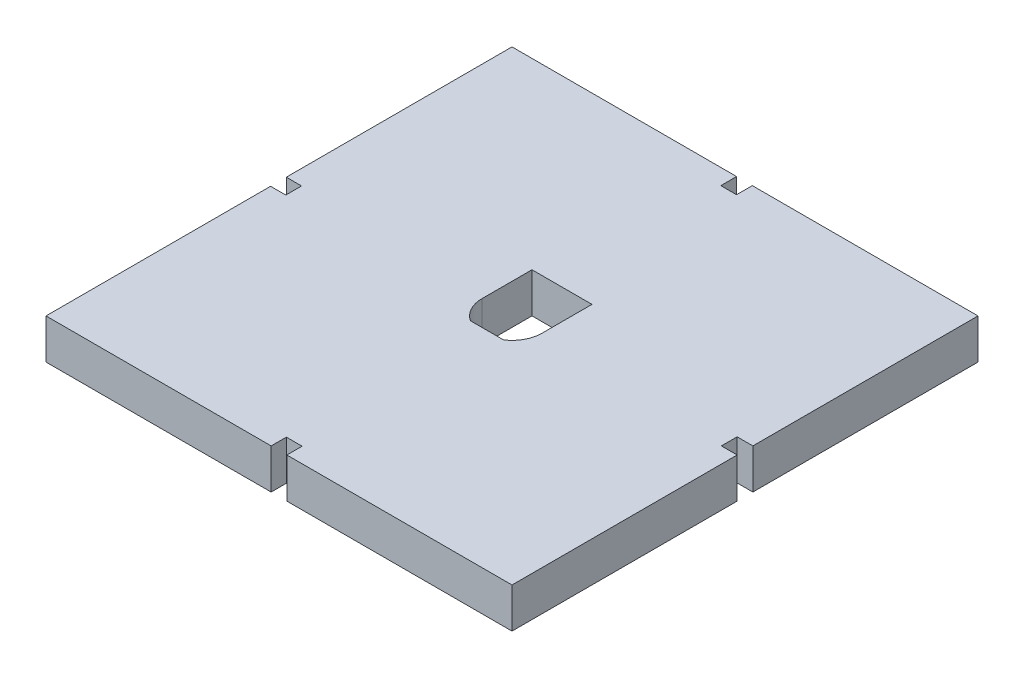
SolidWorks part; units mm, degrees
ref_plane "Front Plane" through (0, 0, 0) normal (0, 0, 1) x (1, 0, 0)
ref_plane "Top Plane" through (0, 0, 0) normal (0, 1, 0) x (1, 0, 0)
ref_plane "Right Plane" through (0, 0, 0) normal (1, 0, 0) x (0, 0, -1)
sketch "Sketch1" plane through (0, 0, 0) normal (0, 1, 0) x (1, 0, 0)
  line L1 (0, 0) -> (148, 0)
  line L2 (0, 0) -> (0, 148)
  line L3 (0, 148) -> (148, 148)
  line L4 (148, 0) -> (148, 148)
  dimension "D1" = 148
  dimension "D2" = 148
extrude "Boss-Extrude1" add sketch "Sketch1" along normal blind 12.7
sketch "Sketch2" plane through (0, 12.7, 0) normal (0, 1, 0) x (1, 0, 0)
  line L0 (74, 148) -> (74, 0) construction
  line L1 (148, 148) -> (0, 148) construction
  line L2 (0, 0) -> (148, 0) construction
  line L3 (0, 74) -> (148, 74) construction
  line L4 (0, 148) -> (0, 0) construction
  line L5 (148, 0) -> (148, 148) construction
  line L7 (83.525, 74) -> (64.475, 74)
  line L8 (83.525, 74) -> (83.525, 89.875)
  line L9 (83.525, 89.875) -> (64.475, 89.875)
  line L10 (64.475, 74) -> (64.475, 89.875)
  line L11 (68.7349, 81.9375) -> (79.2651, 81.9375)
  line L12 (68.7349, 81.9375) -> (68.7349, 66.0625)
  line L13 (68.7349, 66.0625) -> (79.2651, 66.0625)
  line L14 (79.2651, 81.9375) -> (79.2651, 66.0625)
  line L15 (68.7349, 81.9375) -> (79.2651, 66.0625) construction
  line L16 (68.7349, 66.0625) -> (79.2651, 81.9375) construction
  circle A0 centre (74, 74) radius 9.525
  point P22 (74, 66.0625)
  dimension "D1" = 19.05
  dimension "D2" = 19.05
  dimension "D3" = 7.9375
  dimension "D4" = 23.8125
extrude "Cut-Extrude1" cut sketch "Sketch2" against normal blind 12.7 contours A0 L8 L9 L10 | L7 A0 L14 | L12 A0 L7 | L14 L11 L12 L7 | L11 A0 | L14 A0 L7 | L7 A0 L12 | L14 L7 L12 L13
sketch "Sketch4" plane through (0, 12.7, 0) normal (0, 1, 0) x (1, 0, 0)
  line L0 (148, 0) -> (148, 148) construction
  line L1 (143, 71.5) -> (153, 71.5)
  line L2 (143, 71.5) -> (143, 76.5)
  line L3 (143, 76.5) -> (153, 76.5)
  line L4 (153, 71.5) -> (153, 76.5)
  line L5 (143, 71.5) -> (153, 76.5) construction
  line L6 (143, 76.5) -> (153, 71.5) construction
  point P0 (148, 74)
  dimension "D1" = 10
  dimension "D2" = 5
extrude "Cut-Extrude2" cut sketch "Sketch4" against normal through all
ref_point "Point1"
ref_axis "Axis1" through (73.9166, 12.7, -73.9104) along (0, 1, 0)
pattern_circular "CirPattern1" count 4 over 360 about axis through (73.9166, 12.7, -73.9104) along (0, 1, 0) of "Cut-Extrude2"
